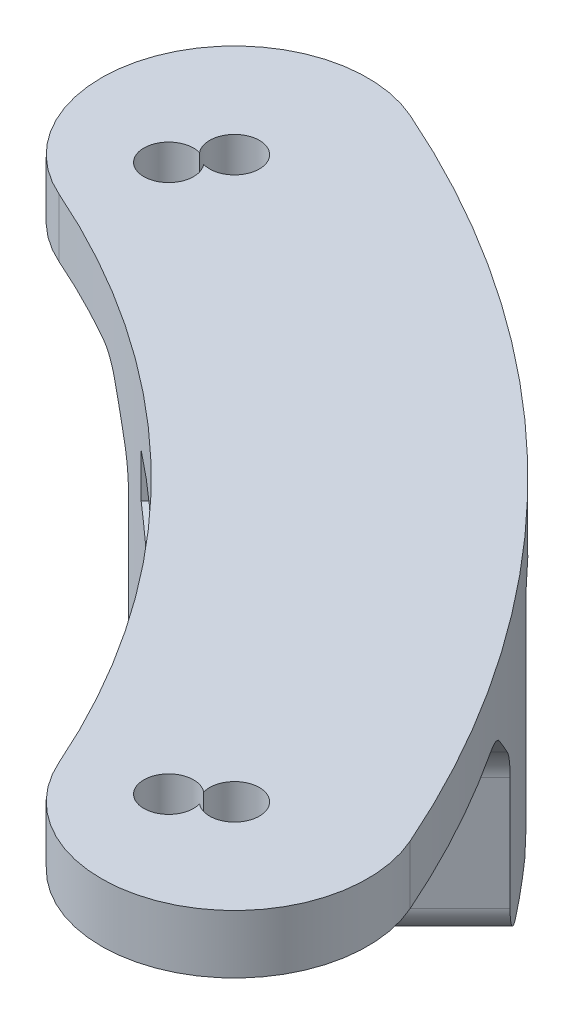
SolidWorks part; units mm, degrees
ref_plane "Front Plane" through (0, 0, 0) normal (0, 0, 1) x (1, 0, 0)
ref_plane "Top Plane" through (0, 0, 0) normal (0, 1, 0) x (1, 0, 0)
ref_plane "Right Plane" through (0, 0, 0) normal (1, 0, 0) x (0, 0, -1)
sketch "Sketch1" plane through (0, -74.9015, 0) normal (0, -1, 0) x (1, 0, 0)
  line L0 (46.4923, -46.4923) -> (47.0891, -47.0891) construction
  line L1 (28.3755, -65.8026) -> (65.8026, -28.3755) construction
  circle A0 centre (28.3755, -65.8026) radius 1.7
  circle A1 centre (65.8026, -28.3755) radius 1.7
  arc A2 (33.8428, -76.8444) -> (76.8444, -33.8428) centre (0, 0) ccw construction
  arc A3 (21.5669, -71.4952) -> (33.8428, -76.8444) centre (30.1717, -68.5087) ccw construction
  arc A4 (26.5006, -60.1729) -> (33.8428, -76.8444) centre (30.1717, -68.5087) ccw construction
  arc A5 (76.8444, -33.8428) -> (60.1729, -26.5006) centre (68.5087, -30.1717) ccw construction
  arc A6 (33.8428, -76.8444) -> (76.8444, -33.8428) centre (0, 0) ccw
  arc A7 (21.5669, -71.4952) -> (33.8428, -76.8444) centre (30.1717, -68.5087) ccw
  arc A8 (26.5006, -60.1729) -> (33.8428, -76.8444) centre (30.1717, -68.5087) ccw
  arc A9 (76.8444, -33.8428) -> (60.1729, -26.5006) centre (68.5087, -30.1717) ccw
  arc A10 (60.1729, -26.5006) -> (26.5006, -60.1729) centre (0, 0) cw
  point P15 (47.0891, -47.0891)
  arc M17 (21.5669, -71.4952) -> (33.8428, -76.8444) centre (30.1717, -68.5087) ccw
  arc M18 (33.8428, -76.8444) -> (76.8444, -33.8428) centre (0, 0) ccw
  arc M19 (76.8444, -33.8428) -> (71.4952, -21.5669) centre (68.5087, -30.1717) ccw
  circle M28 centre (68.5087, -30.1717) radius 1.7
  circle M29 centre (30.1717, -68.5087) radius 1.7
  dimension "D1" = 3.4
  dimension "D2" = 52.93
  dimension "D3" = 71.66
extrude "Boss-Extrude1" add sketch "Sketch1" along normal blind 4 contours A9 A10 A8 M17 M18 M19 M28 M29 region at (51.3283, -74.9015, -51.3283)
ref_plane "Plane1" through (48.1381, 0, -48.1381) normal (0.7071, 0, -0.7071) x (-0.7071, 0, -0.7071)
ref_plane "Plane2" through (62.2802, 0, -62.2802) normal (0.7071, 0, -0.7071) x (-0.7071, 0, -0.7071)
sketch "Sketch2" plane through (62.2802, 0, -62.2802) normal (0.7071, 0, -0.7071) x (-0.7071, 0, -0.7071)
  line L0 (-12, -78.9015) -> (-12, -93.9015)
  line L1 (-30.4067, -78.9015) -> (30.4067, -78.9015) construction
  line L2 (-12, -93.9015) -> (-4, -93.9015)
  line L3 (-4, -93.9015) -> (-4, -78.9015)
  line L4 (-4, -78.9015) -> (-12, -78.9015)
  line L5 (0, -78.9015) -> (0, -94.9061) construction
  line L6 (4, -93.9015) -> (12, -93.9015)
  line L7 (12, -93.9015) -> (12, -78.9015)
  line L8 (12, -78.9015) -> (8, -78.9015)
  line L9 (8, -81.9015) -> (4, -84.2109)
  line L10 (4, -84.2109) -> (4, -93.9015)
  line L11 (8, -78.9015) -> (8, -81.9015)
  dimension "D1" = 8
  dimension "D2" = 15
  dimension "D3" = 8
  dimension "D4" = 3
  dimension "D5" = 120
  dimension "D6" = 4
extrude "Boss-Extrude2" add sketch "Sketch2" against normal blind 30
sketch "Sketch3" plane through (0, -93.9015, 0) normal (0, -1, 0) x (1, 0, 0)
  line L0 (29.4841, -58.7686) -> (22.0629, -51.3475)
  line L1 (22.0629, -51.3475) -> (52.6779, -23.0254)
  line L2 (52.6779, -23.0254) -> (58.6525, -29.7144)
  line L3 (72.7124, -41.9918) -> (86.4476, -52.4176)
  line L4 (86.4476, -52.4176) -> (48.4046, -83.5816)
  line L5 (48.4046, -83.5816) -> (40.7967, -73.3896)
  arc A0 (58.6525, -29.7144) -> (29.4841, -58.7686) centre (0, 0) cw
  circle A1 centre (0, 0) radius 65.75 construction
  arc A2 (72.7124, -41.9918) -> (40.7967, -73.3896) centre (0, 0) cw
  arc A3 (67.2492, -50.2787) -> (76.8444, -33.8428) centre (0, 0) ccw construction
  arc A4 (33.8428, -76.8444) -> (50.2787, -67.2492) centre (0, 0) ccw construction
extrude "Cut-Extrude1" cut sketch "Sketch3" against normal blind 30
sketch "Sketch4" plane through (8.4853, 0, 8.4853) normal (0.7071, 0, 0.7071) x (0.7071, 0, -0.7071)
  line L0 (64.6457, -93.9015) -> (83.1048, -93.9015) construction
  line L1 (65.6282, -78.9015) -> (65.6282, -93.9015) construction
  circle A0 centre (74.1282, -88.9015) radius 1.5
  dimension "D1" = 3
  dimension "D2" = 5
  dimension "D3" = 8.5
extrude "Cut-Extrude2" cut sketch "Sketch4" against normal through all
fillet "Fillet1" radius 2 2 edges at (43.7524, -93.9015, -60.7229) (60.7229, -93.9015, -43.7524)
chamfer "Chamfer1" distance 1 angle 45 2 edges at (55.6845, -93.9015, -50.0276) (50.0276, -93.9015, -55.6845)
chamfer "Chamfer2" distance 4 angle 45 2 edges at (43.7524, -78.9015, -60.7229) (60.7229, -78.9015, -43.7524)
fillet "Fillet2" radius 3 4 edges at (63.0038, -78.9015, -40.3764) (60.7229, -82.9015, -43.7524) (43.7524, -82.9015, -60.7229) (40.3764, -78.9015, -63.0038)
